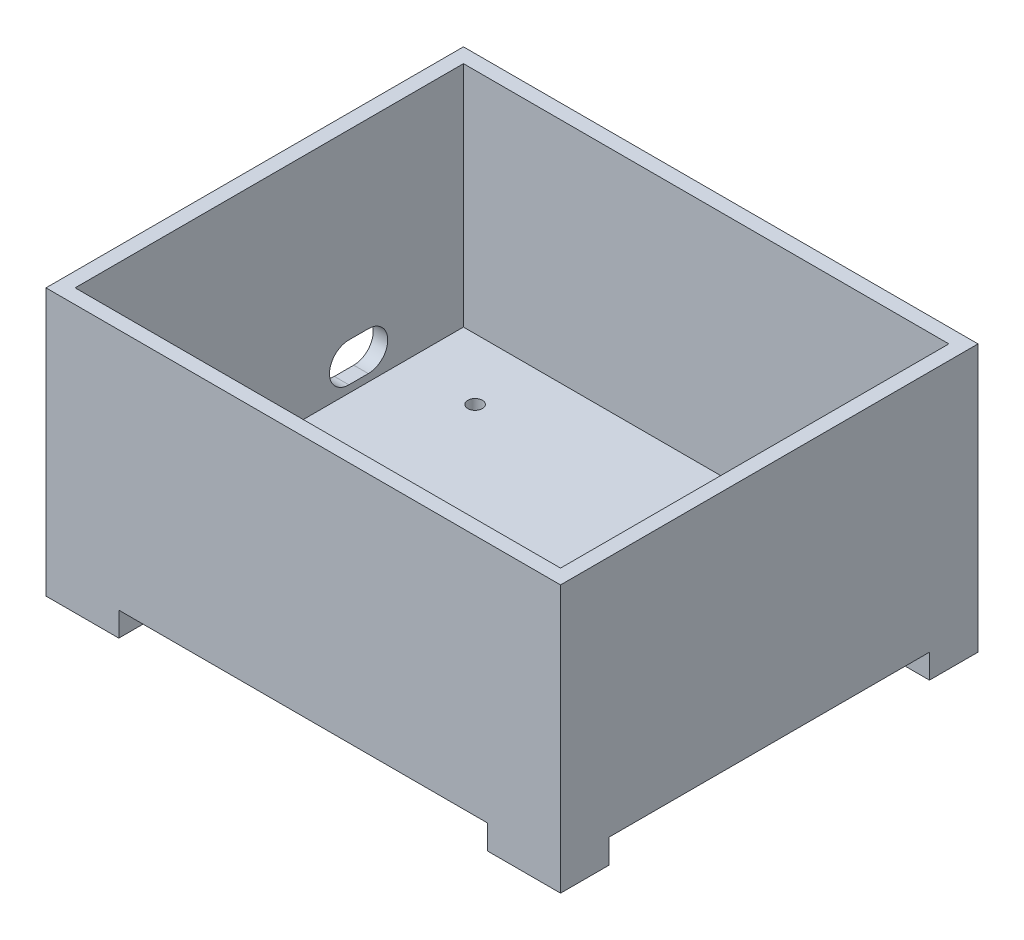
SolidWorks part; units mm, degrees
ref_plane "Piano frontale" through (0, 0, 0) normal (0, 0, 1) x (1, 0, 0)
ref_plane "Piano superiore" through (0, 0, 0) normal (0, 1, 0) x (1, 0, 0)
ref_plane "Piano destro" through (0, 0, 0) normal (1, 0, 0) x (0, 0, -1)
sketch "Schizzo1" plane through (0, 0, 0) normal (0, 1, 0) x (1, 0, 0)
  line L0 (0, 40) -> (100, 40) construction
  line L1 (0, 0) -> (100, 0)
  line L2 (0, 0) -> (0, 80)
  line L3 (0, 80) -> (100, 80)
  line L4 (100, 0) -> (100, 80)
  line L5 (50, 0) -> (50, 80) construction
  line L6 (0, 67.4) -> (100, 67.4) construction
  line L8 (0, 59.25) -> (100, 59.25) construction
  circle A0 centre (15, 67.4) radius 1.5
  circle A1 centre (15, 12.6) radius 1.5
  circle A2 centre (76.979, 59.25) radius 1.5
  circle A3 centre (76.979, 20.75) radius 1.5
  point P21 (76.979, 59.25)
  point P22 (13.5, 67.4)
  dimension "D5" = 3
  dimension "D6" = 15
  dimension "D10" = 3
  dimension "D1" = 100
  dimension "D2" = 80
  dimension "D3" = 12.6
  dimension "D4" = 27.4
  dimension "D7" = 19.25
  dimension "D9" = 64
extrude "Estrusione-Estrusione1" add sketch "Schizzo1" along normal blind 3
ref_plane "Piano1" through (0, 0, -40) normal (0, 0, 1) x (1, 0, 0)
sketch "Schizzo2" plane through (0, 0, 0) normal (0, 0, 1) x (1, 0, 0)
  line L0 (0, 0) -> (100, 0)
  line L1 (0, 0) -> (0, 50)
  line L2 (100, 0) -> (100, 50)
  line L3 (0, 50) -> (100, 50)
  dimension "D1" = 50
extrude "Estrusione-Estrusione2" add sketch "Schizzo2" along normal blind 3
mirror "Specchia1" about plane through (0, 0, -40) normal (0, 0, 1) of "Estrusione-Estrusione2"
ref_plane "Piano2" through (50, 0, 0) normal (1, 0, 0) x (0, 0, -1)
sketch "Schizzo3" plane through (0, 0, 0) normal (-1, 0, 0) x (0, 0, 1)
  line L0 (-83, 0) -> (3, 0)
  line L1 (-83, 0) -> (-83, 50)
  line L2 (3, 0) -> (3, 50)
  line L3 (-83, 50) -> (3, 50)
  line L4 (3, 50) -> (3, 0) construction
  dimension "D1" = 50
extrude "Estrusione-Estrusione3" add sketch "Schizzo3" along normal blind 3
sketch "Schizzo4" plane through (-3, 0, 0) normal (-1, 0, 0) x (0, 0, 1)
  line L2 (-83, 50) -> (-83, 0) construction
  line L3 (-83, 0) -> (3, 0) construction
  line L4 (-60.4, 8.5) -> (-56.4, 8.5) construction
  line L5 (-60.4, 12.5) -> (-56.4, 12.5)
  line L6 (-60.4, 4.5) -> (-56.4, 4.5)
  arc A1 (-60.4, 12.5) -> (-60.4, 4.5) centre (-60.4, 8.5) ccw
  arc A2 (-56.4, 4.5) -> (-56.4, 12.5) centre (-56.4, 8.5) ccw
  point P0 (-64.4, 8.5)
  point P7 (-58.4, 8.5)
  point P12 (-64.4, 8.5)
  point P13 (-52.4, 8.5)
  dimension "D1" = 18.6
  dimension "D2" = 8.5
  dimension "D3" = 12
  dimension "D4" = 8
mirror "Specchia2" about plane through (50, 0, 0) normal (1, 0, 0) of "Estrusione-Estrusione3"
extrude "Taglio-Estrusione1" cut sketch "Schizzo4" against normal blind 10
sketch "Schizzo6" plane through (0, 0, 0) normal (0, -1, 0) x (1, 0, 0)
  line L0 (88, 3) -> (88, -7)
  line L1 (-3, 3) -> (12, 3)
  line L2 (-3, 3) -> (-3, -7)
  line L3 (-3, -7) -> (12, -7)
  line L4 (12, 3) -> (12, -7)
  line L5 (88, 3) -> (103, 3)
  line L6 (103, 3) -> (103, -7)
  line L7 (88, -7) -> (103, -7)
  line L8 (88, -73) -> (88, -83)
  line L9 (88, -73) -> (103, -73)
  line L10 (103, -73) -> (103, -83)
  line L11 (88, -83) -> (103, -83)
  line L12 (-3, -73) -> (-3, -83)
  line L13 (-3, -73) -> (12, -73)
  line L14 (12, -73) -> (12, -83)
  line L15 (-3, -83) -> (12, -83)
  dimension "D1" = 15
  dimension "D2" = 10
  dimension "D3" = 2
  dimension "D4" = 2
extrude "Estrusione-Estrusione4" add sketch "Schizzo6" along normal blind 5
